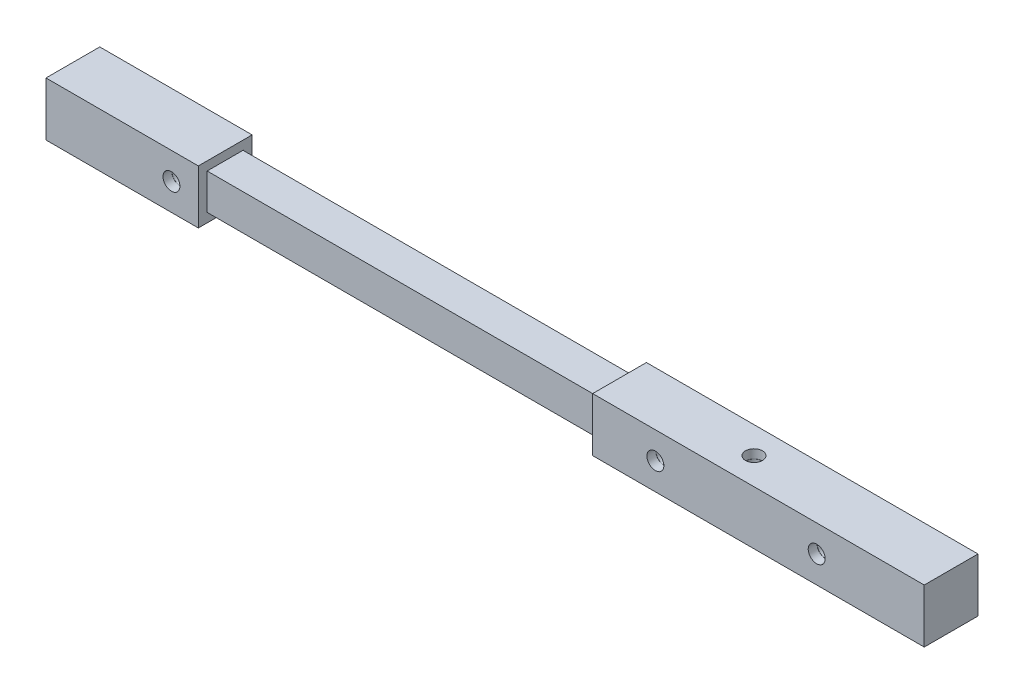
SolidWorks part; units mm, degrees
ref_plane "Front Plane" through (0, 0, 0) normal (0, 0, 1) x (1, 0, 0)
ref_plane "Top Plane" through (0, 0, 0) normal (0, 1, 0) x (1, 0, 0)
ref_plane "Right Plane" through (0, 0, 0) normal (1, 0, 0) x (0, 0, -1)
sketch "Sketch1" plane through (0, 0, 0) normal (1, 0, 0) x (0, 0, -1)
  line L1 (-3.175, -3.175) -> (3.175, -3.175)
  line L2 (-3.175, -3.175) -> (-3.175, 3.175)
  line L3 (-3.175, 3.175) -> (3.175, 3.175)
  line L4 (3.175, -3.175) -> (3.175, 3.175)
  line L5 (-3.175, -3.175) -> (3.175, 3.175) construction
  line L6 (-3.175, 3.175) -> (3.175, -3.175) construction
  point P0 (0, 0)
  dimension "D1" = 6.35
extrude "Boss-Extrude1" add sketch "Sketch1" along normal blind 152.4
sketch "Sketch2" plane through (0, 0, 3.175) normal (0, 0, 1) x (1, 0, 0)
  line L0 (0, 0) -> (20.6375, 0) construction
  line L1 (152.4, 0) -> (134.9375, 0) construction
  line L2 (152.4, 3.175) -> (152.4, -3.175) construction
  line L3 (134.9375, 0) -> (106.3625, 0) construction
  circle A0 centre (20.6375, 0) radius 1.5
  circle A1 centre (134.9375, 0) radius 1.5
  circle A2 centre (106.3625, 0) radius 1.5
  dimension "D2" = 3
  dimension "D1" = 20.6375
  dimension "D3" = 17.4625
  dimension "D4" = 28.575
extrude "Cut-Extrude1" cut sketch "Sketch2" against normal through all
sketch "Sketch3" plane through (0, 3.175, 0) normal (0, 1, 0) x (1, 0, 0)
  line L0 (104.8625, -3.175) -> (107.8625, -3.175) construction
  line L1 (104.8625, -3.175) -> (107.8625, -3.175) construction
  line L2 (106.3625, -3.175) -> (106.3625, 3.175) construction
  line L3 (152.4, 3.175) -> (0, 3.175) construction
  line L4 (106.3625, 0) -> (119.0625, 0) construction
  circle A0 centre (119.0625, 0) radius 1.5
  dimension "D2" = 3
  dimension "D1" = 12.7
extrude "Cut-Extrude2" cut sketch "Sketch3" against normal through all
sketch "Sketch4" plane through (152.4, 0, 0) normal (1, 0, 0) x (0, 0, -1)
  line L1 (4.7625, -4.7625) -> (-4.7625, -4.7625)
  line L2 (4.7625, -4.7625) -> (4.7625, 4.7625)
  line L3 (4.7625, 4.7625) -> (-4.7625, 4.7625)
  line L4 (-4.7625, -4.7625) -> (-4.7625, 4.7625)
  line L5 (4.7625, -4.7625) -> (-4.7625, 4.7625) construction
  line L6 (4.7625, 4.7625) -> (-4.7625, -4.7625) construction
  line L20 (3.2004, -3.2004) -> (3.2004, 3.2004)
  line L21 (-3.2004, -3.2004) -> (3.2004, -3.2004)
  line L22 (-3.2004, 3.2004) -> (-3.2004, -3.2004)
  line L23 (3.2004, 3.2004) -> (-3.2004, 3.2004)
  line L24 (3.2004, -3.2004) -> (3.2004, 3.2004)
  line L25 (-3.2004, -3.2004) -> (3.2004, -3.2004)
  line L26 (-3.2004, 3.2004) -> (-3.2004, -3.2004)
  line L27 (3.2004, 3.2004) -> (-3.2004, 3.2004)
  point P0 (0, 0)
  dimension "D1" = 9.525
  dimension "D2" = 0.0254
extrude "Boss-Extrude2" add sketch "Sketch4" against normal blind 57.15 separate body
sketch "Sketch5" plane through (152.4, 0, 0) normal (1, 0, 0) x (0, 0, -1)
  line L4 (-4.7625, 4.7625) -> (-4.7625, -4.7625)
  line L5 (-4.7625, -4.7625) -> (4.7625, -4.7625)
  line L6 (4.7625, -4.7625) -> (4.7625, 4.7625)
  line L7 (4.7625, 4.7625) -> (-4.7625, 4.7625)
  line L8 (-4.7625, 4.7625) -> (-4.7625, -4.7625)
  line L9 (-4.7625, -4.7625) -> (4.7625, -4.7625)
  line L10 (4.7625, -4.7625) -> (4.7625, 4.7625)
  line L11 (4.7625, 4.7625) -> (-4.7625, 4.7625)
  dimension "D1" = 0
extrude "Boss-Extrude3" add sketch "Sketch5" along normal blind 1.5875
sketch "Sketch6" plane through (0, 0, 3.175) normal (0, 0, 1) x (1, 0, 0)
  circle A0 centre (134.9375, 0) radius 1.5 construction
  circle A1 centre (106.3625, 0) radius 1.5 construction
  circle A2 centre (134.9375, 0) radius 1.5
  circle A3 centre (106.3625, 0) radius 1.5
extrude "Cut-Extrude4" cut sketch "Sketch6" against normal through all both and the other way through all
sketch "Sketch7" plane through (0, 3.175, 0) normal (0, 1, 0) x (1, 0, 0)
  circle A0 centre (119.0625, 0) radius 1.5 construction
  circle A1 centre (119.0625, 0) radius 1.5
extrude "Cut-Extrude6" cut sketch "Sketch7" against normal through all both and the other way through all
sketch "Sketch8" plane through (0, 0, 0) normal (-1, 0, 0) x (0, 0, 1)
  line L0 (3.2004, 3.2004) -> (3.2004, -3.2004) construction
  line L1 (3.2004, -3.2004) -> (-3.2004, -3.2004) construction
  line L2 (-3.2004, -3.2004) -> (-3.2004, 3.2004) construction
  line L3 (-3.2004, 3.2004) -> (3.2004, 3.2004) construction
  line L4 (4.7625, -4.7625) -> (4.7625, 4.7625)
  line L5 (4.7625, 4.7625) -> (-4.7625, 4.7625)
  line L6 (-4.7625, 4.7625) -> (-4.7625, -4.7625)
  line L7 (-4.7625, -4.7625) -> (4.7625, -4.7625)
  line L8 (4.7625, -4.7625) -> (4.7625, 4.7625)
  line L9 (4.7625, 4.7625) -> (-4.7625, 4.7625)
  line L10 (-4.7625, 4.7625) -> (-4.7625, -4.7625)
  line L11 (-4.7625, -4.7625) -> (4.7625, -4.7625)
  line L12 (3.2004, 3.2004) -> (3.2004, -3.2004)
  line L13 (3.2004, -3.2004) -> (-3.2004, -3.2004)
  line L14 (-3.2004, -3.2004) -> (-3.2004, 3.2004)
  line L15 (-3.2004, 3.2004) -> (3.2004, 3.2004)
  dimension "D1" = 0
extrude "Boss-Extrude4" add sketch "Sketch8" against normal blind 25.4 separate body
sketch "Sketch9" plane through (0, 0, 0) normal (-1, 0, 0) x (0, 0, 1)
  line L4 (-4.7625, -4.7625) -> (4.7625, -4.7625)
  line L5 (4.7625, -4.7625) -> (4.7625, 4.7625)
  line L6 (4.7625, 4.7625) -> (-4.7625, 4.7625)
  line L7 (-4.7625, 4.7625) -> (-4.7625, -4.7625)
  line L8 (-4.7625, -4.7625) -> (4.7625, -4.7625)
  line L9 (4.7625, -4.7625) -> (4.7625, 4.7625)
  line L10 (4.7625, 4.7625) -> (-4.7625, 4.7625)
  line L11 (-4.7625, 4.7625) -> (-4.7625, -4.7625)
  dimension "D1" = 0
extrude "Boss-Extrude5" add sketch "Sketch9" along normal blind 1.5875
sketch "Sketch10" plane through (0, 0, 3.175) normal (0, 0, 1) x (1, 0, 0)
  circle A0 centre (20.6375, 0) radius 1.5 construction
  circle A1 centre (20.6375, 0) radius 1.5
extrude "Cut-Extrude8" cut sketch "Sketch10" against normal through all both and the other way through all
